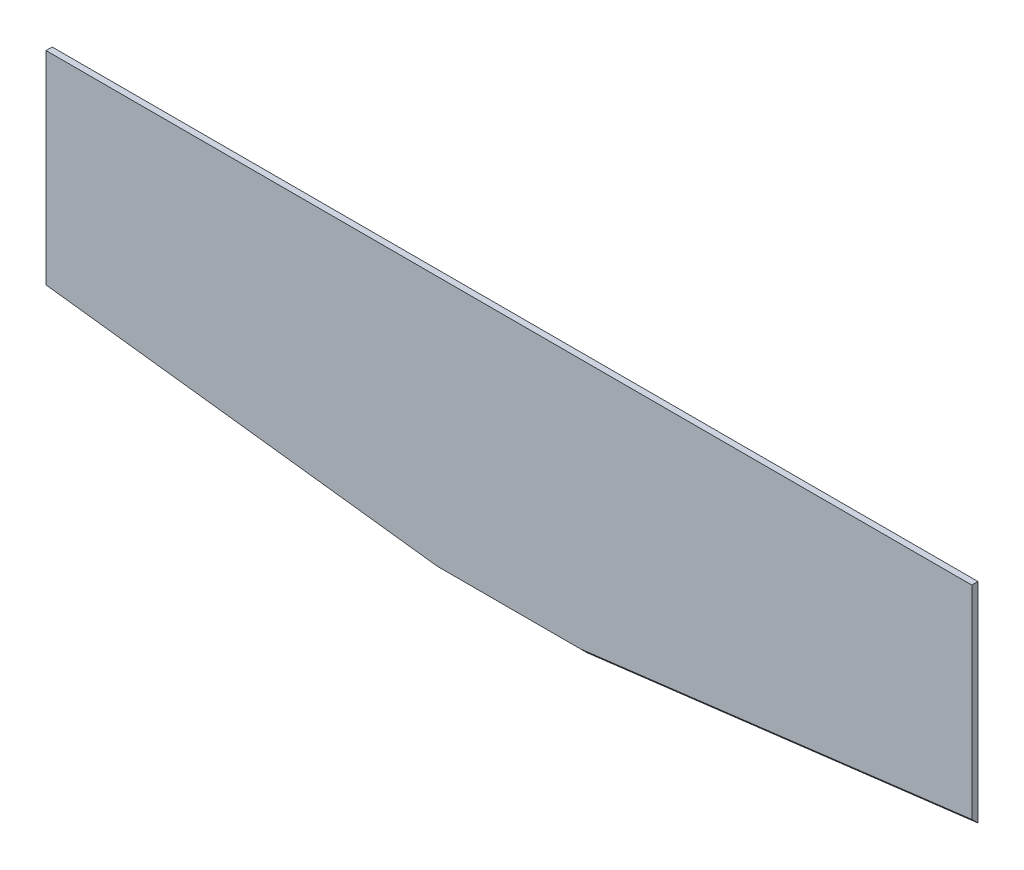
SolidWorks part; units mm, degrees
ref_plane "前视基准面" through (0, 0, 0) normal (0, 0, 1) x (1, 0, 0)
ref_plane "上视基准面" through (0, 0, 0) normal (0, 1, 0) x (1, 0, 0)
ref_plane "右视基准面" through (0, 0, 0) normal (1, 0, 0) x (0, 0, -1)
other "Configuration Table"
sketch "草图1" plane through (0, 0, 0) normal (0, 0, 1) x (1, 0, 0)
  line L1 (-14, 9) -> (76, 9)
  line L2 (-14, 9) -> (-14, -16)
  line L3 (-14, -16) -> (76, -16)
  line L4 (76, 9) -> (76, -16)
  circle A0 centre (0, 0) radius 3.75 construction
  circle A1 centre (63.5, 0) radius 3.75 construction
  dimension "D1" = 7.5
  dimension "D2" = 16
  dimension "D3" = 9
  dimension "D5" = 76
  dimension "D6" = 63.5
  dimension "D4" = 14
extrude "凸台-拉伸1" add sketch "草图1" along normal blind 0.6
sketch "草图2" plane through (0, 0, 0.6) normal (0, 0, 1) x (1, 0, 0)
  line L3 (24, -16) -> (-14, -11.3342)
  line L4 (-14, 9) -> (-14, -16) construction
  line L5 (-14, -11.3342) -> (-14, -16)
  line L6 (-14, -16) -> (24, -16)
  line L7 (31, 9) -> (31, -16) construction
  line L8 (76, 9) -> (-14, 9) construction
  line L9 (-14, -16) -> (76, -16) construction
  line L10 (76, -11.3342) -> (76, -16)
  line L11 (38, -16) -> (76, -11.3342)
  line L12 (76, -16) -> (38, -16)
  point P1 (31, -16)
  point P6 (-14, -16)
  dimension "D1" = 7
  dimension "D2" = 7
extrude "切除-拉伸1" cut sketch "草图2" against normal up to next
chamfer "倒角1" distance 0.6 angle 45 3 edges at (57, -13.6671, 0.6) (5, -13.6671, 0.6) (31, -16, 0.6)
